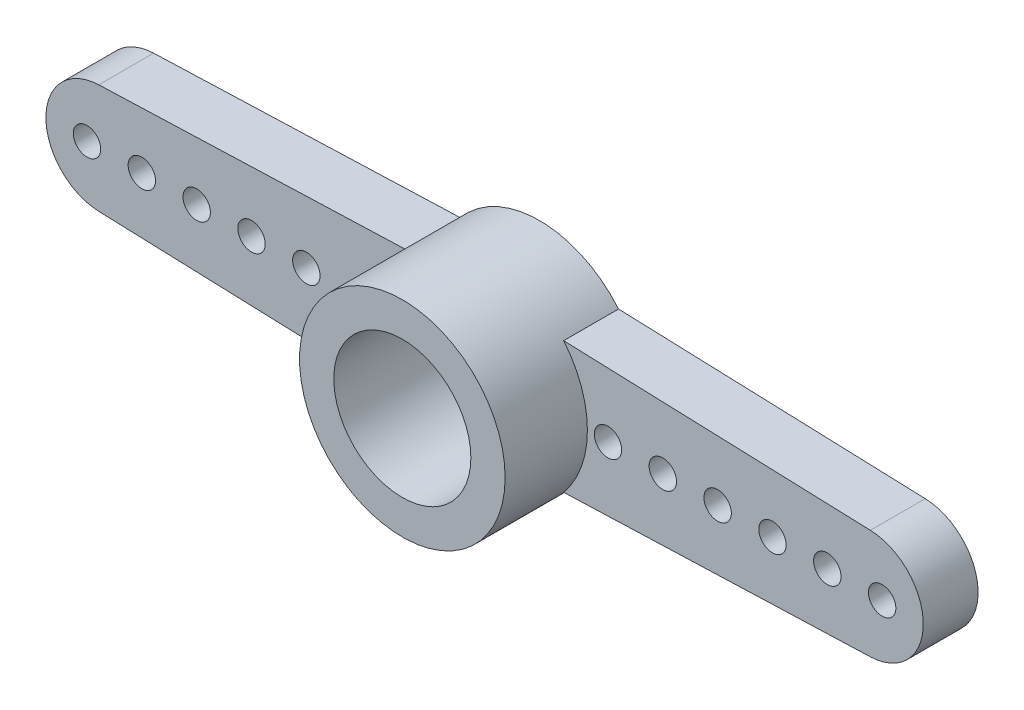
SolidWorks part; units mm, degrees
ref_plane "Спереди" through (0, 0, 0) normal (0, 0, 1) x (1, 0, 0)
ref_plane "Сверху" through (0, 0, 0) normal (0, 1, 0) x (1, 0, 0)
ref_plane "Справа" through (0, 0, 0) normal (1, 0, 0) x (0, 0, -1)
sketch "Эскиз1" plane through (0, 0, 0) normal (0, 0, 1) x (1, 0, 0)
  line L0 (0, 0) -> (-14, 0)
  line L1 (-14.0708, 1.9987) -> (0, 2.4974)
  line L2 (-14.0708, -1.9987) -> (0, -2.4974)
  line L4 (14.0708, -1.9987) -> (0, -2.4974)
  line L5 (14.0708, 1.9987) -> (0, 2.4974)
  circle A0 centre (0, 0) radius 3.75
  circle A1 centre (0, 0) radius 2.5
  arc A2 (-13.967, -1.9997) -> (-14.0708, 1.9987) centre (-14, 0) cw
  arc A3 (13.967, -1.9997) -> (14.0708, 1.9987) centre (14, 0) ccw
  dimension "D1" = 7.5
  dimension "D2" = 5
  dimension "D4" = 2
  dimension "D3" = 14
extrude "Бобышка-Вытянуть3" add sketch "Эскиз1" along normal blind 2 contours L4 A3 L5 A0 | A2 L2 A0 L1 region at (-3.6586, -1.3206, 0) region at (9.339, 0, 0)
sketch "Эскиз2" plane through (0, 0, 2) normal (0, 0, 1) x (1, 0, 0)
  circle A0 centre (0, 0) radius 3.75
  circle A1 centre (0, 0) radius 2.5
  dimension "D1" = 5
extrude "Бобышка-Вытянуть5" add sketch "Эскиз2" along normal blind 3 separate body
sketch "Эскиз3" plane through (0, 0, 2) normal (0, 0, -1) x (-1, 0, 0)
  circle A0 centre (0, 0) radius 3.75
  circle A1 centre (0, 0) radius 2.5
extrude "Бобышка-Вытянуть6" add sketch "Эскиз3" along normal blind 2
sketch "Эскиз4" plane through (0, 0, 0) normal (0, 0, -1) x (-1, 0, 0)
  line L0 (-16, 0) -> (-14.5, 0)
  line L1 (-14.5, 0) -> (-12.5, 0)
  line L2 (-12.5, 0) -> (-10.5, 0)
  line L3 (-10.5, 0) -> (-8.5, 0)
  line L4 (-8.5, 0) -> (-6.5, 0)
  line L5 (-6.5, 0) -> (-4.5, 0)
  arc A0 (-14.0708, 1.9987) -> (-14.0708, -1.9987) centre (-14, 0) ccw construction
  circle A1 centre (-14.5, 0) radius 0.5
  circle A2 centre (-12.5, 0) radius 0.5
  circle A3 centre (-10.5, 0) radius 0.5
  circle A4 centre (-8.5, 0) radius 0.5
  circle A5 centre (-6.5, 0) radius 0.5
  circle A6 centre (-4.5, 0) radius 0.5
  circle A7 centre (4.5, 0) radius 0.5
  circle A8 centre (6.5, 0) radius 0.5
  circle A9 centre (8.5, 0) radius 0.5
  circle A10 centre (10.5, 0) radius 0.5
  circle A11 centre (12.5, 0) radius 0.5
  circle A12 centre (14.5, 0) radius 0.5
  dimension "D2" = 1
  dimension "D8" = 1
  dimension "D9" = 1
  dimension "D10" = 1
  dimension "D11" = 1
  dimension "D12" = 1
  dimension "D1" = 1.5
  dimension "D3" = 2
  dimension "D4" = 2
  dimension "D5" = 2
  dimension "D6" = 2
  dimension "D7" = 2
extrude "Вырез-Вытянуть1" cut sketch "Эскиз4" against normal blind 2 contours L1 A1 L0 | L0 A1 L1 | L3 A3 L2 | L2 A3 L3 | L4 A4 L3 | L3 A4 L4 | L5 A5 L4 | L4 A5 L5 | A6 | A7 | A8 | A9 | A10 | A11 | A12 | A2 | A12 region at (14.5, 0.2122, 0) region at (4.5, 0.4859, 0) region at (6.5, 0.2122, 0) region at (6.5, -0.2122, 0) region at (8.5, 0.2122, 0) region at (8.5, -0.2122, 0) region at (10.5, 0.2122, 0) region at (10.5, -0.2122, 0) region at (14.5, -0.2122, 0) region at (-4.5, 0, 0) region at (-6.5, 0, 0) region at (-8.5, 0, 0) region at (-10.5, 0, 0) region at (-12.5, 0, 0) region at (-14.5, 0, 0)
sketch "Эскиз5" plane through (0, 0, 0) normal (0, 0, -1) x (-1, 0, 0)
  circle A0 centre (0, 0) radius 2.5
extrude "Бобышка-Вытянуть7" add sketch "Эскиз5" against normal blind 1
sketch "Эскиз6" plane through (0, 0, 0) normal (0, 0, -1) x (-1, 0, 0)
  circle A0 centre (0, 0) radius 2.5
  dimension "D1" = 5
extrude "Вырез-Вытянуть2" cut sketch "Эскиз6" against normal blind 0.5
sketch "Эскиз7" plane through (0, 0, 0.5) normal (0, 0, -1) x (-1, 0, 0)
  circle A0 centre (0, 0) radius 1.25
  dimension "D1" = 2.5
extrude "Вырез-Вытянуть3" cut sketch "Эскиз7" against normal blind 5
sketch "Эскиз8" plane through (0, 0, 0.5) normal (0, 0, -1) x (-1, 0, 0)
  line L0 (-2.8252, -0.1999) -> (-2.8894, -0.2509)
